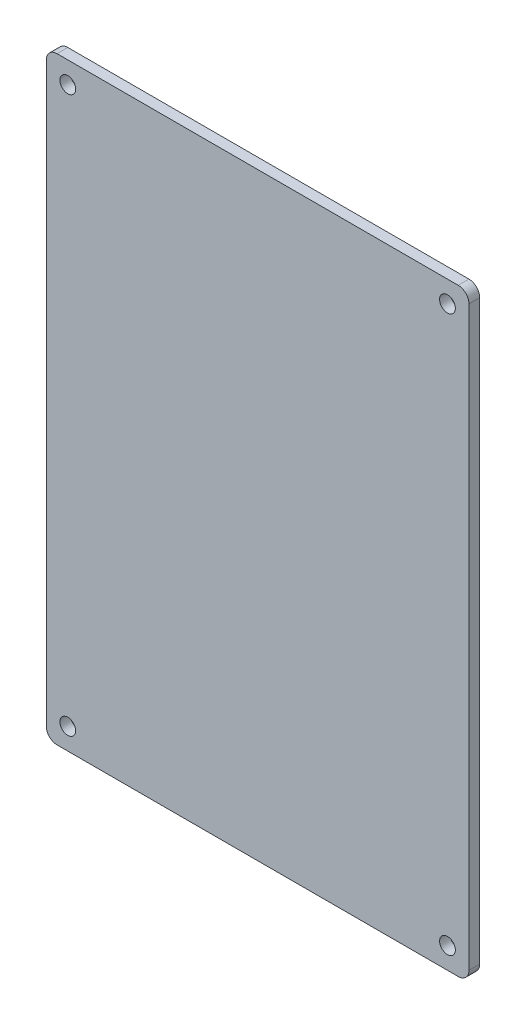
SolidWorks part; units mm, degrees
ref_plane "Plan de face" through (0, 0, 0) normal (0, 0, 1) x (1, 0, 0)
ref_plane "Plan de dessus" through (0, 0, 0) normal (0, 1, 0) x (1, 0, 0)
ref_plane "Plan de droite" through (0, 0, 0) normal (1, 0, 0) x (0, 0, -1)
sketch "Esquisse3" plane through (0, 0, 13) normal (0, 0, 1) x (1, 0, 0)
  line L4 (-14.3355, 46.8744) -> (-14.3355, -33.7056)
  line L5 (-12.8355, -35.2056) -> (43.1745, -35.2056)
  line L6 (44.6745, -33.7056) -> (44.6745, 46.8744)
  line L7 (43.1745, 48.3744) -> (-12.8355, 48.3744)
  line L8 (-14.3355, 46.8744) -> (-14.3355, -33.7056)
  line L9 (-12.8355, -35.2056) -> (43.1745, -35.2056)
  line L10 (44.6745, -33.7056) -> (44.6745, 46.8744)
  line L11 (43.1745, 48.3744) -> (-12.8355, 48.3744)
  arc A4 (-14.3355, -33.7056) -> (-12.8355, -35.2056) centre (-12.8355, -33.7056) ccw
  arc A5 (43.1745, -35.2056) -> (44.6745, -33.7056) centre (43.1745, -33.7056) ccw
  arc A6 (44.6745, 46.8744) -> (43.1745, 48.3744) centre (43.1745, 46.8744) ccw
  arc A7 (-12.8355, 48.3744) -> (-14.3355, 46.8744) centre (-12.8355, 46.8744) ccw
  arc A8 (-14.3355, -33.7056) -> (-12.8355, -35.2056) centre (-12.8355, -33.7056) ccw
  arc A9 (43.1745, -35.2056) -> (44.6745, -33.7056) centre (43.1745, -33.7056) ccw
  arc A10 (44.6745, 46.8744) -> (43.1745, 48.3744) centre (43.1745, 46.8744) ccw
  arc A11 (-12.8355, 48.3744) -> (-14.3355, 46.8744) centre (-12.8355, 46.8744) ccw
  dimension "D1" = 0
extrude "Lid_Base" add sketch "Esquisse3" along normal blind 1.5
sketch "Esquisse4" plane through (0, 0, 13) normal (0, 0, -1) x (-1, 0, 0)
  line L12 (7.1355, 44.6744) -> (-37.4745, 44.6744)
  line L13 (-37.4745, 44.6744) -> (-37.4745, 43.8744)
  line L14 (-40.1745, 41.1744) -> (-40.9745, 41.1744)
  line L15 (-40.9745, 41.1744) -> (-40.9745, -28.0056)
  line L16 (-40.9745, -28.0056) -> (-40.1745, -28.0056)
  line L17 (-37.4745, -30.7056) -> (-37.4745, -31.5056)
  line L18 (-37.4745, -31.5056) -> (7.1355, -31.5056)
  line L19 (7.1355, -31.5056) -> (7.1355, -30.7056)
  line L20 (9.8355, -28.0056) -> (10.6355, -28.0056)
  line L21 (10.6355, -28.0056) -> (10.6355, 41.1744)
  line L22 (10.6355, 41.1744) -> (9.8355, 41.1744)
  line L23 (7.1355, 43.8744) -> (7.1355, 44.6744)
  line L72 (7.3355, 45.8744) -> (-37.6745, 45.8744)
  line L73 (-38.6745, 44.8744) -> (-38.6745, 43.8744)
  line L74 (-40.1745, 42.3744) -> (-41.1745, 42.3744)
  line L75 (-42.1745, 41.3744) -> (-42.1745, -28.2056)
  line L76 (-41.1745, -29.2056) -> (-40.1745, -29.2056)
  line L77 (-38.6745, -30.7056) -> (-38.6745, -31.7056)
  line L78 (-37.6745, -32.7056) -> (7.3355, -32.7056)
  line L79 (8.3355, -31.7056) -> (8.3355, -30.7056)
  line L80 (9.8355, -29.2056) -> (10.8355, -29.2056)
  line L81 (11.8355, -28.2056) -> (11.8355, 41.3744)
  line L82 (10.8355, 42.3744) -> (9.8355, 42.3744)
  line L83 (8.3355, 43.8744) -> (8.3355, 44.8744)
  line L84 (7.3355, 45.8744) -> (-37.6745, 45.8744)
  line L85 (-38.6745, 44.8744) -> (-38.6745, 43.8744)
  line L86 (-40.1745, 42.3744) -> (-41.1745, 42.3744)
  line L87 (-42.1745, 41.3744) -> (-42.1745, -28.2056)
  line L88 (-41.1745, -29.2056) -> (-40.1745, -29.2056)
  line L89 (-38.6745, -30.7056) -> (-38.6745, -31.7056)
  line L90 (-37.6745, -32.7056) -> (7.3355, -32.7056)
  line L91 (8.3355, -31.7056) -> (8.3355, -30.7056)
  line L92 (9.8355, -29.2056) -> (10.8355, -29.2056)
  line L93 (11.8355, -28.2056) -> (11.8355, 41.3744)
  line L94 (10.8355, 42.3744) -> (9.8355, 42.3744)
  line L95 (8.3355, 43.8744) -> (8.3355, 44.8744)
  arc A12 (-37.4745, 44.6744) -> (-37.4745, 44.6744) centre (-37.4745, 44.6744) ccw
  arc A13 (-40.1745, 41.1744) -> (-37.4745, 43.8744) centre (-40.1745, 43.8744) ccw
  arc A15 (-40.9745, 41.1744) -> (-40.9745, 41.1744) centre (-40.9745, 41.1744) ccw
  arc A17 (-40.9745, -28.0056) -> (-40.9745, -28.0056) centre (-40.9745, -28.0056) ccw
  arc A19 (-37.4745, -30.7056) -> (-40.1745, -28.0056) centre (-40.1745, -30.7056) ccw
  arc A21 (-37.4745, -31.5056) -> (-37.4745, -31.5056) centre (-37.4745, -31.5056) ccw
  arc A22 (7.1355, -31.5056) -> (7.1355, -31.5056) centre (7.1355, -31.5056) ccw
  arc A23 (9.8355, -28.0056) -> (7.1355, -30.7056) centre (9.8355, -30.7056) ccw
  arc A76 (-37.6745, 45.8744) -> (-38.6745, 44.8744) centre (-37.6745, 44.8744) ccw
  arc A77 (-40.1745, 42.3744) -> (-38.6745, 43.8744) centre (-40.1745, 43.8744) ccw
  arc A78 (-41.1745, 42.3744) -> (-42.1745, 41.3744) centre (-41.1745, 41.3744) ccw
  arc A79 (-42.1745, -28.2056) -> (-41.1745, -29.2056) centre (-41.1745, -28.2056) ccw
  arc A80 (-38.6745, -30.7056) -> (-40.1745, -29.2056) centre (-40.1745, -30.7056) ccw
  arc A81 (-38.6745, -31.7056) -> (-37.6745, -32.7056) centre (-37.6745, -31.7056) ccw
  arc A82 (7.3355, -32.7056) -> (8.3355, -31.7056) centre (7.3355, -31.7056) ccw
  arc A83 (9.8355, -29.2056) -> (8.3355, -30.7056) centre (9.8355, -30.7056) ccw
  arc A84 (10.8355, -29.2056) -> (11.8355, -28.2056) centre (10.8355, -28.2056) ccw
  arc A85 (11.8355, 41.3744) -> (10.8355, 42.3744) centre (10.8355, 41.3744) ccw
  arc A86 (8.3355, 43.8744) -> (9.8355, 42.3744) centre (9.8355, 43.8744) ccw
  arc A87 (8.3355, 44.8744) -> (7.3355, 45.8744) centre (7.3355, 44.8744) ccw
  arc A88 (-37.6745, 45.8744) -> (-38.6745, 44.8744) centre (-37.6745, 44.8744) ccw
  arc A89 (-40.1745, 42.3744) -> (-38.6745, 43.8744) centre (-40.1745, 43.8744) ccw
  arc A90 (-41.1745, 42.3744) -> (-42.1745, 41.3744) centre (-41.1745, 41.3744) ccw
  arc A91 (-42.1745, -28.2056) -> (-41.1745, -29.2056) centre (-41.1745, -28.2056) ccw
  arc A92 (-38.6745, -30.7056) -> (-40.1745, -29.2056) centre (-40.1745, -30.7056) ccw
  arc A93 (-38.6745, -31.7056) -> (-37.6745, -32.7056) centre (-37.6745, -31.7056) ccw
  arc A94 (7.3355, -32.7056) -> (8.3355, -31.7056) centre (7.3355, -31.7056) ccw
  arc A95 (9.8355, -29.2056) -> (8.3355, -30.7056) centre (9.8355, -30.7056) ccw
  arc A96 (10.8355, -29.2056) -> (11.8355, -28.2056) centre (10.8355, -28.2056) ccw
  arc A97 (11.8355, 41.3744) -> (10.8355, 42.3744) centre (10.8355, 41.3744) ccw
  arc A98 (8.3355, 43.8744) -> (9.8355, 42.3744) centre (9.8355, 43.8744) ccw
  arc A99 (8.3355, 44.8744) -> (7.3355, 45.8744) centre (7.3355, 44.8744) ccw
  arc A100 (10.6355, -28.0056) -> (10.6355, -28.0056) centre (10.6355, -28.0056) ccw
  arc A101 (10.6355, 41.1744) -> (10.6355, 41.1744) centre (10.6355, 41.1744) ccw
  arc A102 (7.1355, 43.8744) -> (9.8355, 41.1744) centre (9.8355, 43.8744) ccw
  arc A103 (7.1355, 44.6744) -> (7.1355, 44.6744) centre (7.1355, 44.6744) ccw
  dimension "D1" = 0
  dimension "D2" = 1.2
extrude "Insert" add sketch "Esquisse4" along normal blind 2
fillet "Congé1" radius 1 8 edges at (-10.6355, 6.5844, 13) (-7.9263, -28.7964, 13) (15.1695, -31.5056, 13) (38.2653, -28.7964, 13) (40.9745, 6.5844, 13) (38.2653, 41.9652, 13) (15.1695, 44.6744, 13) (-7.9263, 41.9652, 13)
sketch "Esquisse5" plane through (0, 0, 14.5) normal (0, 0, 1) x (1, 0, 0)
  circle A0 centre (-11.3355, -32.2056) radius 1.1 construction
  circle A1 centre (-11.3355, -32.2056) radius 1.1
  circle A2 centre (-11.3355, 45.3744) radius 1.1 construction
  circle A3 centre (41.6745, 45.3744) radius 1.1 construction
  circle A4 centre (41.6745, -32.2056) radius 1.1 construction
  circle A5 centre (-11.3355, 45.3744) radius 1.1
  circle A6 centre (41.6745, 45.3744) radius 1.1
  circle A7 centre (41.6745, -32.2056) radius 1.1
extrude "M3_Hole" cut sketch "Esquisse5" against normal up to next
